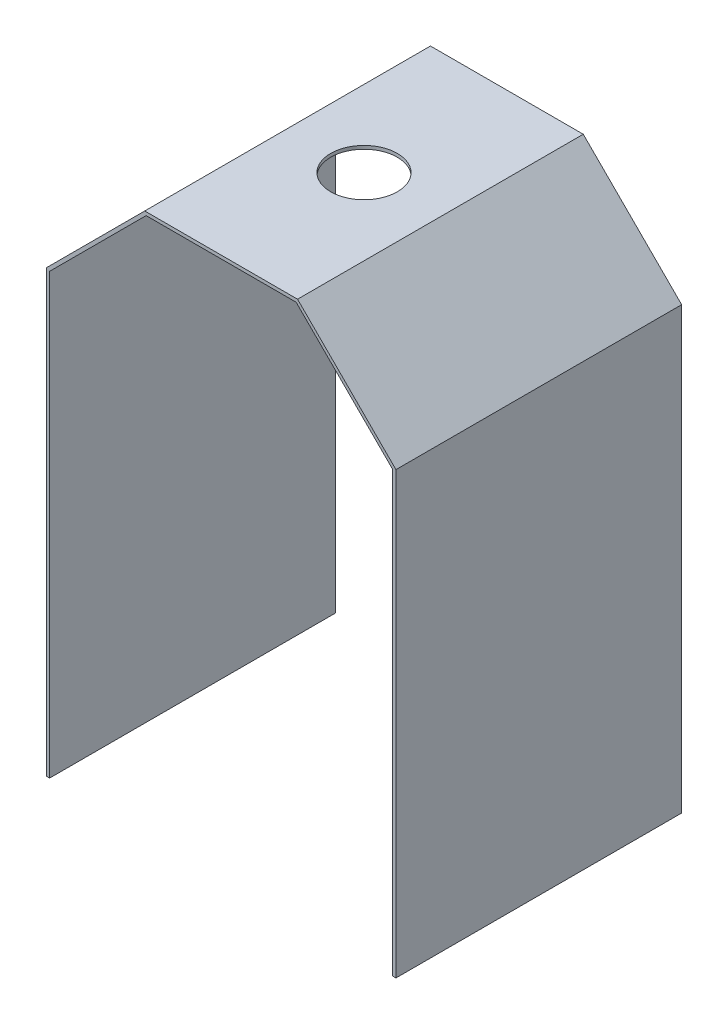
SolidWorks part; units mm, degrees
ref_plane "Спереди" through (0, 0, 0) normal (0, 0, 1) x (1, 0, 0)
ref_plane "Сверху" through (0, 0, 0) normal (0, 1, 0) x (1, 0, 0)
ref_plane "Справа" through (0, 0, 0) normal (1, 0, 0) x (0, 0, -1)
sketch "Эскиз1" plane through (0, 0, 0) normal (0, 0, 1) x (1, 0, 0)
  line L2 (-96.7252, 314.9265) -> (-96.7252, 579.3926)
  line L3 (-96.7252, 579.3926) -> (-37.6214, 638.4965)
  line L4 (-37.6214, 638.4965) -> (54.1709, 638.4965)
  line L5 (54.1709, 638.4965) -> (113.2748, 579.3926)
  line L6 (113.2748, 579.3926) -> (113.2748, 314.9265)
extrude "Вытянуть-Тонкостенный1" add sketch "Эскиз1" along normal blind 171.62 thin thin type one direction wall 2
sketch "Эскиз2" plane through (0, 638.4965, 0) normal (0, 1, 0) x (1, 0, 0)
  circle A0 centre (8.2748, -85.81) radius 20
extrude "Вырез-Вытянуть1" cut sketch "Эскиз2" against normal through all
